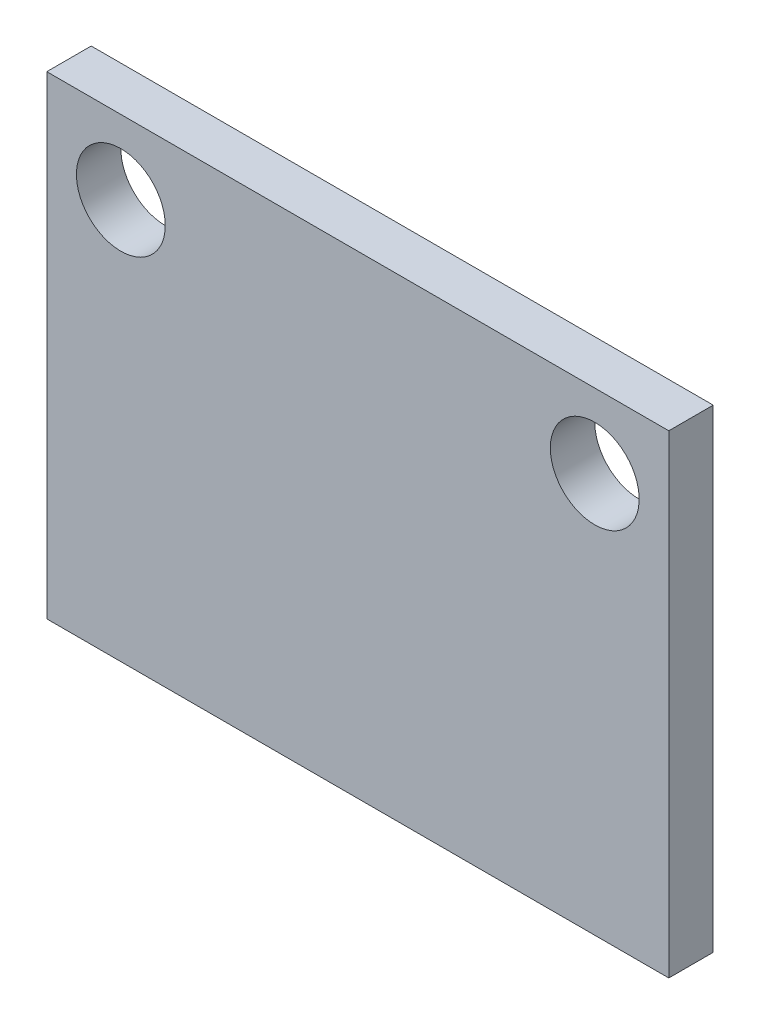
SolidWorks part; units mm, degrees
ref_plane "Alzado" through (0, 0, 0) normal (0, 0, 1) x (1, 0, 0)
ref_plane "Planta" through (0, 0, 0) normal (0, 1, 0) x (1, 0, 0)
ref_plane "Vista lateral" through (0, 0, 0) normal (1, 0, 0) x (0, 0, -1)
sketch "Croquis1" plane through (0, 0, 0) normal (0, 0, 1) x (1, 0, 0)
  line L0 (0, 0) -> (0, 8) construction
  line L1 (10.5, -8) -> (-10.5, -8)
  line L2 (10.5, -8) -> (10.5, 8)
  line L3 (10.5, 8) -> (-10.5, 8)
  line L4 (-10.5, -8) -> (-10.5, 8)
  line L5 (10.5, -8) -> (-10.5, 8) construction
  line L6 (10.5, 8) -> (-10.5, -8) construction
  circle A0 centre (-8, 5.5) radius 1.5
  circle A1 centre (8, 5.5) radius 1.5
  point P0 (0, 0)
  dimension "D3" = 3
  dimension "D1" = 16
  dimension "D2" = 21
  dimension "D4" = 2.5
  dimension "D5" = 2.5
extrude "Saliente-Extruir1" add sketch "Croquis1" along normal blind 1.5
